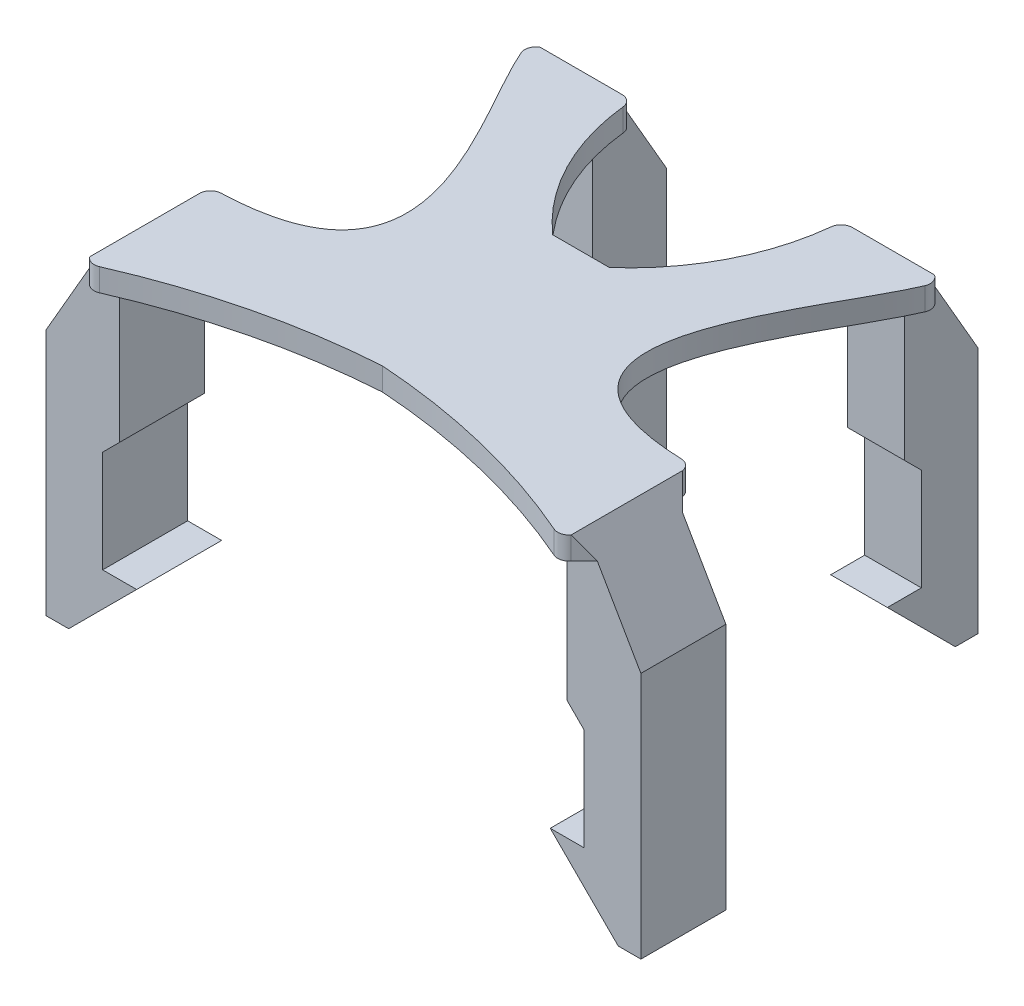
SolidWorks part; units mm, degrees
ref_plane "Front Plane" through (0, 0, 0) normal (0, 0, 1) x (1, 0, 0)
ref_plane "Top Plane" through (0, 0, 0) normal (0, 1, 0) x (1, 0, 0)
ref_plane "Right Plane" through (0, 0, 0) normal (1, 0, 0) x (0, 0, -1)
sketch "Sketch1" plane through (0, 0, 0) normal (0, 1, 0) x (1, 0, 0)
  line L1 (-21.25, -22.25) -> (21.25, -22.25)
  line L2 (-21.25, -22.25) -> (-21.25, 22.25)
  line L3 (-21.25, 22.25) -> (21.25, 22.25)
  line L4 (21.25, -22.25) -> (21.25, 22.25)
  line L5 (-21.25, -22.25) -> (21.25, 22.25) construction
  line L6 (-21.25, 22.25) -> (21.25, -22.25) construction
  point P0 (0, 0)
  dimension "D1" = 42.5
  dimension "D2" = 44.5
extrude "Boss-Extrude1" add sketch "Sketch1" along normal blind 2
sketch "Sketch2" plane through (0, 0, -22.25) normal (0, 0, -1) x (-1, 0, 0)
  line L0 (21.25, -22.5) -> (18.25, -22.5)
  line L2 (21.25, 2) -> (21.25, 0)
  line L4 (26.25, -6.6603) -> (26.25, -18)
  line L5 (18.25, -22.5) -> (24.25, -28.5)
  line L6 (24.25, -28.5) -> (26.25, -28.5)
  line L7 (26.25, -28.5) -> (26.25, -18)
  line L8 (21.25, 0) -> (19.75, 0)
  line L9 (-21.25, 0) -> (21.25, 0) construction
  line L10 (19.75, 0) -> (19.75, -12)
  line L12 (21.25, -13.5) -> (21.25, -22.5)
  line L13 (21.25, -13.5) -> (19.75, -12)
  line L14 (21.25, 2) -> (26.25, -6.6603)
  dimension "D1" = 5
  dimension "D2" = 60
  dimension "D3" = 1.5
  dimension "D4" = 3
  dimension "D5" = 2
  dimension "D6" = 45
  dimension "D7" = 12
  dimension "D8" = 9
extrude "Boss-Extrude2" add sketch "Sketch2" against normal blind 7.5 from offset 27.25 offset against normal yes
mirror "Mirror1" about plane through (0, 0, 0) normal (1, 0, 0) of "Boss-Extrude2"
sketch "Sketch3" plane through (0, 0, 5) normal (0, 0, -1) x (-1, 0, 0)
  line L20 (-21.25, 2) -> (-26.25, -6.6603)
  line L21 (-26.25, -6.6603) -> (-26.25, -28.5)
  line L22 (-26.25, -28.5) -> (-24.25, -28.5)
  line L23 (-24.25, -28.5) -> (-18.25, -22.5)
  line L24 (-18.25, -22.5) -> (-21.25, -22.5)
  line L25 (-21.25, -22.5) -> (-21.25, -13.5)
  line L26 (-21.25, -13.5) -> (-19.75, -12)
  line L27 (-19.75, -12) -> (-19.75, 0)
  line L28 (-19.75, 0) -> (-21.25, 0)
  line L29 (-21.25, 0) -> (-21.25, 2)
  line L30 (-21.25, 2) -> (-26.25, -6.6603)
  line L31 (-26.25, -6.6603) -> (-26.25, -28.5)
  line L32 (-26.25, -28.5) -> (-24.25, -28.5)
  line L33 (-24.25, -28.5) -> (-18.25, -22.5)
  line L34 (-18.25, -22.5) -> (-21.25, -22.5)
  line L35 (-21.25, -22.5) -> (-21.25, -13.5)
  line L36 (-21.25, -13.5) -> (-19.75, -12)
  line L37 (-19.75, -12) -> (-19.75, 0)
  line L38 (-19.75, 0) -> (-21.25, 0)
  line L39 (-21.25, 0) -> (-21.25, 2)
  dimension "D1" = 0
sketch "Sketch4" plane through (21.25, 0, 0) normal (1, 0, 0) x (0, 0, -1)
  line L1 (27.25, -6.6603) -> (27.25, -28.5)
  line L10 (22.25, 0) -> (22.25, 2)
  line L11 (20.75, 0) -> (22.25, 0)
  line L12 (20.75, -12) -> (20.75, 0)
  line L13 (22.25, -13.5) -> (20.75, -12)
  line L14 (22.25, -22.5) -> (22.25, -13.5)
  line L15 (19.25, -22.5) -> (22.25, -22.5)
  line L16 (25.25, -28.5) -> (19.25, -22.5)
  line L17 (27.25, -28.5) -> (25.25, -28.5)
  line L18 (22.25, 2) -> (27.25, -6.6603)
  line L19 (22.25, 2) -> (22.25, 0) construction
  line L22 (-5, 0) -> (22.25, 0) construction
  dimension "D1" = 12
  dimension "D2" = 9
  dimension "D3" = 10.5
  dimension "D4" = 5
  dimension "D5" = 2
  dimension "D6" = 60
  dimension "D7" = 45
  dimension "D8" = 45
  dimension "D9" = 21.8397
  dimension "D10" = 6
extrude "Boss-Extrude3" add sketch "Sketch4" against normal blind 5 from offset 5 offset against normal yes
mirror "Mirror2" about plane through (0, 0, 0) normal (1, 0, 0) of "Boss-Extrude3"
sketch "Sketch5" plane through (0, 2, 0) normal (0, 1, 0) x (1, 0, 0)
  line L0 (-21.25, -14.5) -> (-21.25, -3)
  line L1 (-9.25, 22.25) -> (-18.25, 22.25)
  line L2 (-21.25, 22.25) -> (-21.25, -5) construction
  line L3 (0, -9.063) -> (0, -22.25)
  line L4 (-16.25, 22.25) -> (-21.25, 22.25) construction
  line L5 (-26.25, -5) -> (-21.25, -5) construction
  line L6 (-26.25, -12.5) -> (-21.25, -12.5) construction
  line L7 (-16.25, 27.25) -> (-16.25, 22.25) construction
  line L8 (-11.25, 27.25) -> (-11.25, 22.25) construction
  line L9 (0, 30.214) -> (0, -31.9518) construction
  line L10 (0, -22.25) -> (-21.25, -22.25)
  line L11 (-21.25, -22.25) -> (-21.25, 22.25)
  line L12 (-21.25, 22.25) -> (21.25, 22.25)
  line L13 (11.25, 22.25) -> (-11.25, 22.25) construction
  line L14 (0, 22.25) -> (0, -9.063)
  line L15 (21.25, -22.25) -> (21.25, 22.25)
  line L16 (0, -22.25) -> (21.25, -22.25)
  line L17 (-2.5, 8.4682) -> (2.5, 8.4682)
  line L18 (-21.25, -22.25) -> (21.25, -22.25) construction
  arc A0 (-21.25, -14.5) -> (0, -9.063) centre (3.9968, -68.9298) cw
  arc A1 (-9.25, 22.25) -> (-2.5, 8.4682) centre (10.712, 23.4829) ccw
  arc A2 (21.25, -14.5) -> (0, -9.063) centre (-3.9968, -68.9298) ccw
  arc A3 (9.25, 22.25) -> (2.5, 8.4682) centre (-10.712, 23.4829) cw
  spline S0 degree 3 poles (-18.25, 22.25) (-16.8183, 16.4186) (-0.0363, -2.8775) (-21.25, -3) knots 0 0 0 0 1 1 1 1
  spline S1 degree 3 poles (18.25, 22.25) (16.8183, 16.4186) (0.0363, -2.8775) (21.25, -3) knots 0 0 0 0 1 1 1 1
  point P3 (-21.25, -8.75)
  point P8 (-13.75, 22.25)
  dimension "D5" = 60
  dimension "D6" = 20
  dimension "D7" = 5
  dimension "D1" = 2
  dimension "D2" = 2
  dimension "D3" = 2
  dimension "D4" = 2
extrude "Cut-Extrude3" cut sketch "Sketch5" against normal blind 5 contours S0 L16 L17 | L12 A1 L17 L14 | A3 L12 L14 L17 | L12 S1 L15 | L3 A2 L16 | A0 S0 L10 L3 region at (-9.7689, 2, 16.5543) region at (-16.9758, 2, -8.0325) region at (9.7689, 2, 16.5543) region at (-3.7771, 2, -16.4193) region at (3.7771, 2, -16.4193) region at (16.9758, 2, -8.0325)
chamfer "Chamfer1" distance 1.15 angle 45 8 edges at (-21.25, 1, 12.5) (-11.25, 1, -22.25) (-16.25, 1, -22.25) (11.25, 1, -22.25) (16.25, 1, -22.25) (21.25, 1, 5) (21.25, 1, 12.5) (-21.25, 1, 5)
fillet "Fillet1" radius 1 8 edges at (-21.25, 1, 3) (-18.25, 1, -22.25) (-9.25, 1, -22.25) (9.25, 1, -22.25) (18.25, 1, -22.25) (21.25, 1, 3) (21.25, 1, 14.5) (-21.25, 1, 14.5)
